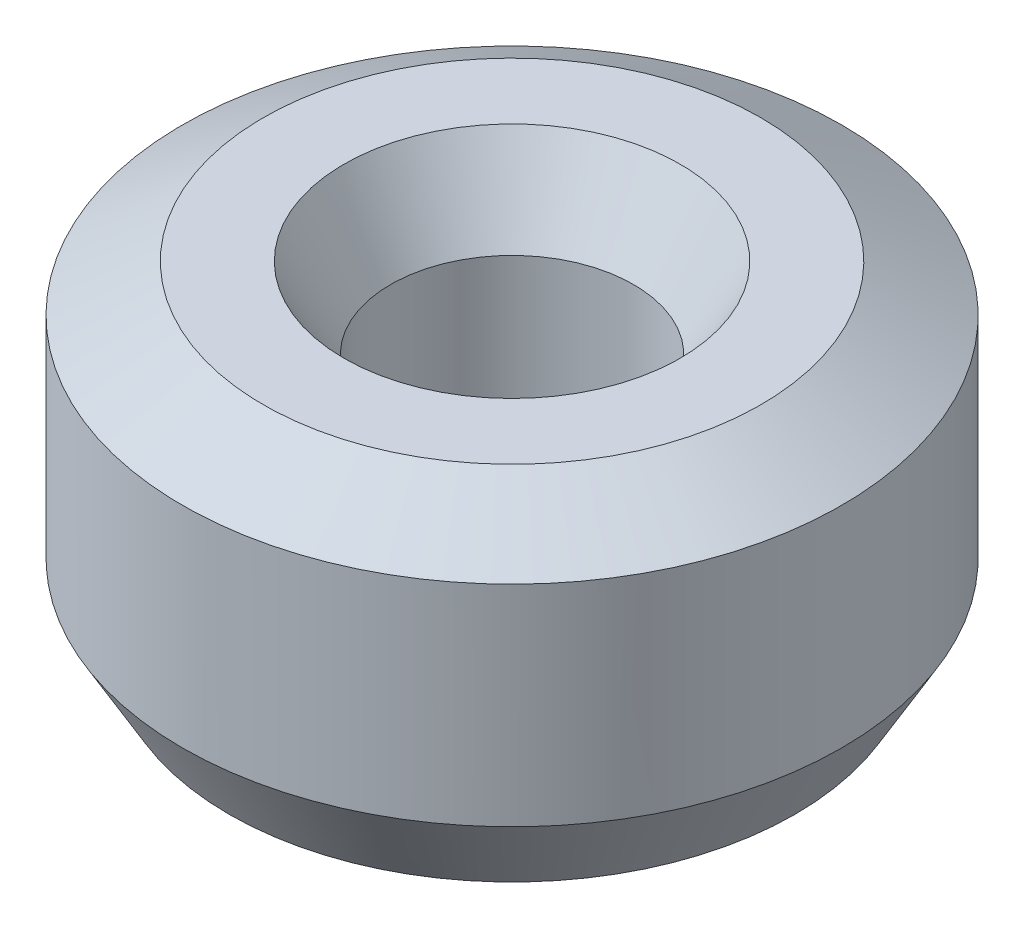
SolidWorks part; units mm, degrees
ref_plane "Front Plane" through (0, 0, 0) normal (0, 0, 1) x (1, 0, 0)
ref_plane "Top Plane" through (0, 0, 0) normal (0, 1, 0) x (1, 0, 0)
ref_plane "Right Plane" through (0, 0, 0) normal (1, 0, 0) x (0, 0, -1)
sketch "Sketch1" plane through (0, 0, 0) normal (0, 1, 0) x (1, 0, 0)
  circle A0 centre (0, 0) radius 12.5
  dimension "SLEEVE_OD" = 25
extrude "Boss-Extrude1" add sketch "Sketch1" along normal blind 12.8059
sketch "Sketch2" plane through (0, 0, 0) normal (0, 1, 0) x (1, 0, 0)
  circle A0 centre (0, 0) radius 4.6065
  dimension "BORE_D" = 9.2129
extrude "Cut-Extrude1" cut sketch "Sketch2" along normal through all
chamfer "Chamfer1" distance 1.7704 angle 60 4 edges at (0, 12.8059, 4.6065) (0, 0, 4.6065) (0, 0, 12.5) (0, 12.8059, 12.5) first distance on face at (0, 12.8059, 4.6065) first distance on face at (0, 0, 4.6065) first distance on face at (0, 12.8059, 12.5)
